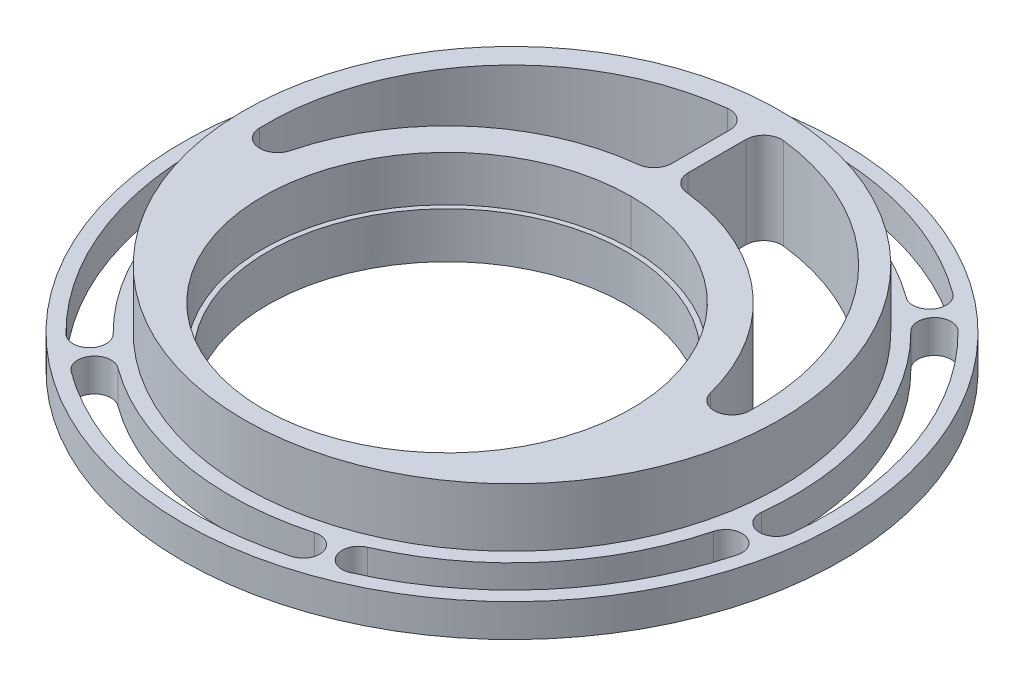
SolidWorks part; units mm, degrees
material "7075-T6, Plate (SS)"
ref_plane "X-Y Datum" through (0, 0, 0) normal (0, 0, 1) x (1, 0, 0)
ref_plane "X-Z Datum" through (0, 0, 0) normal (0, 1, 0) x (1, 0, 0)
ref_plane "Y-Z Datum" through (0, 0, 0) normal (1, 0, 0) x (0, 0, -1)
sketch "Sketch1" plane through (0, 0, 0) normal (0, 1, 0) x (1, 0, 0)
  line L0 (0, 0) -> (0, -12.7) construction
  line L1 (0, -43.0151) -> (0, 43.0151) construction
  line L2 (0, 61.9125) -> (0, 52.3875)
  circle A0 centre (0, -12.7) radius 35.052
  circle A1 centre (0, 0) radius 52.3875 construction
  circle A2 centre (0, 0) radius 57.15 construction
  circle A3 centre (0, 0) radius 61.9125
  point P12 (0, 57.15)
  dimension "D2" = 70.104
  dimension "D3" = 104.775
  dimension "D4" = 123.825
  dimension "D5" = 114.3
  dimension "D1" = 12.7
extrude "Boss-Extrude1" add sketch "Sketch1" along normal blind 4.5212 contours A3 A0 region at (-42.5405, 0, 42.5405)
sketch "Sketch3" plane through (0, 4.5212, 0) normal (0, 1, 0) x (1, 0, 0)
  circle A0 centre (0, 0) radius 52.3875 construction
  circle A1 centre (0, 0) radius 52.3875
extrude "Boss-Extrude2" add sketch "Sketch3" along normal blind 11.43
sketch "Sketch4" plane through (0, 0, 0) normal (0, -1, 0) x (1, 0, 0)
  circle A0 centre (0, 12.7) radius 35.052 construction
  circle A1 centre (0, 12.7) radius 35.052
extrude "Cut-Extrude1" cut sketch "Sketch4" against normal through all
sketch "Sketch9" plane through (0, 15.9512, 0) normal (0, 1, 0) x (1, 0, 0)
  circle A0 centre (0, -12.7) radius 35.052 construction
  circle A1 centre (0, -12.7) radius 35.052 construction
  circle A2 centre (0, -12.7) radius 36
  dimension "D1" = 72
extrude "Cut-Extrude3" cut sketch "Sketch9" against normal blind 8.89
ref_point "Point1"
ref_plane "Plane1" through (0, 0, 0) normal (1, 0, 0) x (0, 0, -1)
split line "Split Line1"
ref_plane "Plane2" through (0, 7.9756, 0) normal (0, 1, 0) x (1, 0, 0)
sketch "Sketch14" plane through (0, 7.9756, 0) normal (0, 1, 0) x (1, 0, 0)
  circle A0 centre (-33.2491, 22.3603) radius 8.255
ref_point "Point4"
ref_point "Point6"
sketch "Sketch10" plane through (0, 15.9512, 0) normal (0, 1, 0) x (1, 0, 0)
  circle A0 centre (0, 0) radius 52.3875 construction
  circle A1 centre (0, 0) radius 52.3875 construction
  arc A7 (0, -52.764) -> (0, 27.364) centre (0, -12.7) ccw
  arc A8 (0, 27.364) -> (0, -52.764) centre (0, -12.7) ccw
  arc A9 (0, -52.764) -> (0, 27.364) centre (0, -12.7) ccw construction
  arc A10 (0, 27.364) -> (0, -52.764) centre (0, -12.7) ccw construction
  circle A29 centre (0, 0) radius 48.3235 construction
  arc A30 (-30.6977, 13.0444) -> (30.6977, 13.0444) centre (0, -12.7) cw
  arc A31 (-43.3761, 21.2996) -> (43.3761, 21.2996) centre (0, 0) cw
  arc A34 (-30.6977, 13.0444) -> (-43.3761, 21.2996) centre (-36.5363, 17.9409) cw
  arc A35 (43.3761, 21.2996) -> (30.6977, 13.0444) centre (36.5363, 17.9409) cw
  dimension "D3" = 7.62
  dimension "D1" = 4.064
  dimension "D2" = 4.064
extrude "Cut-Extrude5" [suppressed] cut sketch "Sketch10" against normal through all contours A35 A31 A34 A30
sketch "Sketch15" [suppressed] plane through (0, 7.9756, 0) normal (0, 1, 0) x (1, 0, 0)
  line L1 (-2.1171, 31.2835) -> (-2.1171, 43.3958)
  line L4 (2.032, 31.291) -> (2.032, 43.4389)
  line L6 (-2.1764, 48.3235) -> (-2.1667, 48.2749) construction
  line L8 (2.1667, 48.2749) -> (2.1764, 48.3235) construction
  arc A0 (30.6977, 13.0444) -> (-30.6977, 13.0444) centre (0, -12.7) ccw construction
  arc A1 (30.6977, 13.0444) -> (-30.6977, 13.0444) centre (0, -12.7) ccw construction
  arc A2 (43.3761, 21.2996) -> (-43.3761, 21.2996) centre (0, 0) ccw construction
  arc A3 (-2.1171, 43.3958) -> (-6.9062, 47.8275) centre (-6.5621, 43.3958) ccw
  arc A4 (43.3761, 21.2996) -> (-43.3761, 21.2996) centre (0, 0) ccw construction
  arc A5 (6.5037, 47.8838) -> (2.032, 43.4389) centre (6.477, 43.4389) ccw
  arc A7 (-2.1171, 31.2835) -> (-5.362, 27.0036) centre (-6.5621, 31.2835) cw
  arc A9 (2.032, 31.291) -> (5.2509, 27.0184) centre (6.477, 31.291) ccw
  arc A10 (-6.9062, 47.8275) -> (6.5037, 47.8838) centre (0, 0) cw
  arc A11 (-5.362, 27.0036) -> (5.2509, 27.0184) centre (0, -12.7) cw
  point P9 (0, 37.4715)
  dimension "D1" = 4.445
  dimension "D2" = 2.1171
  dimension "D3" = 4.445
  dimension "D4" = 2.032
  dimension "D5" = 43.4389
  dimension "D6" = 31.2835
  dimension "D7" = 2.1171
  dimension "D8" = 12.148
  dimension "D9" = 12.1123
extrude "Boss-Extrude3" [suppressed] add sketch "Sketch15" along normal up to surface and the other way up to surface contours A9 L4 A5 A10 A3 L1 A7 A11
sketch "Sketch20" plane through (0, 4.5212, 0) normal (0, 1, 0) x (1, 0, 0)
  circle A0 centre (0, 0) radius 52.3875
  circle A2 centre (0, 0) radius 66.6087
sketch "Sketch25" [suppressed] plane through (0, 15.9512, 0) normal (0, 1, 0) x (1, 0, 0)
  line L6 (-4.6571, 31.2835) -> (-4.6571, 43.3958)
  line L7 (-4.6571, 31.2835) -> (-4.6571, 43.3958)
  line L12 (4.572, 43.4389) -> (4.572, 31.291)
  line L13 (4.572, 43.4389) -> (4.572, 31.291)
  circle A1 centre (-51.685, -7.6867) radius 0.134
  circle A2 centre (49.3335, -18.9489) radius 0.46
  arc A3 (48.8818, -18.8622) -> (48.9404, -18.71) centre (-0.2183, 0.1504) ccw
  arc A4 (48.8818, -18.8622) -> (48.9404, -18.71) centre (-0.2183, 0.1504) ccw
  arc A45 (-4.6571, 43.3958) -> (-6.6423, 45.2991) centre (-6.5621, 43.3958) ccw
  arc A46 (-5.9167, 29.4912) -> (-4.6571, 31.2835) centre (-6.5621, 31.2835) ccw
  arc A47 (-5.9167, 29.4912) -> (-32.6439, 14.6766) centre (0, -12.7) ccw
  arc A48 (-41.0962, 20.18) -> (-32.6439, 14.6766) centre (-36.5363, 17.9409) ccw
  arc A49 (-6.6423, 45.2991) -> (-41.0962, 20.18) centre (0, 0) ccw
  arc A50 (-4.6571, 43.3958) -> (-6.6423, 45.2991) centre (-6.5621, 43.3958) ccw
  arc A51 (-5.9167, 29.4912) -> (-4.6571, 31.2835) centre (-6.5621, 31.2835) ccw
  arc A52 (-5.9167, 29.4912) -> (-32.6439, 14.6766) centre (0, -12.7) ccw
  arc A53 (-41.0962, 20.18) -> (-32.6439, 14.6766) centre (-36.5363, 17.9409) ccw
  arc A54 (-6.6423, 45.2991) -> (-41.0962, 20.18) centre (0, 0) ccw
  circle A68 centre (-0.2183, 0.1504) radius 52.1224
  circle A69 centre (0, -12.7) radius 32.512
  circle A70 centre (0, -12.7) radius 32.512
  arc A72 (32.6439, 14.6766) -> (41.0962, 20.18) centre (36.5363, 17.9409) ccw
  arc A73 (4.572, 31.291) -> (5.8124, 29.5056) centre (6.477, 31.291) ccw
  arc A74 (32.6439, 14.6766) -> (5.8124, 29.5056) centre (0, -12.7) ccw
  arc A75 (41.0962, 20.18) -> (6.3564, 45.3401) centre (0, 0) ccw
  arc A76 (6.3564, 45.3401) -> (4.572, 43.4389) centre (6.477, 43.4389) ccw
  arc A77 (32.6439, 14.6766) -> (41.0962, 20.18) centre (36.5363, 17.9409) ccw
  arc A78 (4.572, 31.291) -> (5.8124, 29.5056) centre (6.477, 31.291) ccw
  arc A79 (32.6439, 14.6766) -> (5.8124, 29.5056) centre (0, -12.7) ccw
  arc A80 (41.0962, 20.18) -> (6.3564, 45.3401) centre (0, 0) ccw
  arc A81 (6.3564, 45.3401) -> (4.572, 43.4389) centre (6.477, 43.4389) ccw
  arc M3 (30.6977, 13.0444) -> (5.2509, 27.0184) centre (0, -12.7) ccw
  arc M4 (5.2509, 27.0184) -> (2.032, 31.291) centre (6.477, 31.291) cw
  line M5 (2.032, 31.291) -> (2.032, 43.4389)
  arc M6 (2.032, 43.4389) -> (6.5037, 47.8838) centre (6.477, 43.4389) cw
  arc M7 (6.5037, 47.8838) -> (43.3761, 21.2996) centre (0, 0) cw
  arc M8 (43.3761, 21.2996) -> (30.6977, 13.0444) centre (36.5363, 17.9409) cw
  arc M9 (-5.362, 27.0036) -> (-30.6977, 13.0444) centre (0, -12.7) ccw
  arc M10 (-30.6977, 13.0444) -> (-43.3761, 21.2996) centre (-36.5363, 17.9409) cw
  arc M11 (-43.3761, 21.2996) -> (-6.9062, 47.8275) centre (0, 0) cw
  arc M12 (-6.9062, 47.8275) -> (-2.1171, 43.3958) centre (-6.5621, 43.3958) cw
  line M13 (-2.1171, 43.3958) -> (-2.1171, 31.2835)
  arc M14 (-2.1171, 31.2835) -> (-5.362, 27.0036) centre (-6.5621, 31.2835) cw
  arc M15 (0, 23.3) -> (0, -48.7) centre (0, -12.7) cw
  arc M16 (0, -48.7) -> (0, 23.3) centre (0, -12.7) cw
  dimension "D1" = 2.54
  dimension "D2" = 2.54
  dimension "D3" = 2.54
extrude "Boss-Extrude5" [suppressed] add sketch "Sketch25" along normal blind 1.27 contours A54 A50 L7 A51 A52 A53 M9 M14 M13 M12 M11 M10 | A70 M15 M16 | A68 A1 M16 M15 M14 M9 M10 M11 M12 M13 M8 M3 M4 M5 M6 M7 | A81 A80 A77 A79 A78 L13 M3 M8 M7 M6 M5 M4
ref_axis "Axis1" [suppressed] through (0, 0, 0) along (0, 0, -1)
sketch "Sketch26" plane through (0, 4.5212, 0) normal (0, 1, 0) x (1, 0, 0)
  line L0 (0, 0) -> (-57.7152, 9.6181)
  line L1 (0, 0) -> (-38.741, -43.8484)
  arc A0 (-58.0713, 6.3737) -> (-41.0626, -41.5543) centre (0, 0) ccw construction
  arc A1 (-61.3157, 6.7298) -> (-43.3568, -43.8759) centre (0, 0) ccw
  arc A2 (-54.8269, 6.0176) -> (-38.7685, -39.2327) centre (0, 0) ccw
  arc A3 (-54.8269, 6.0176) -> (-61.3157, 6.7298) centre (-58.0713, 6.3737) ccw
  arc A4 (-43.3568, -43.8759) -> (-38.7685, -39.2327) centre (-41.0626, -41.5543) ccw
  point P4 (-55.0559, -19.5382)
  dimension "D2" = 3.2639
  dimension "D4" = 6.5278
  dimension "D1" = 58.42
  dimension "D3" = 58
extrude "Cut-Extrude6" cut sketch "Sketch26" against normal up to surface (4.5212 mm away) contours A2 A4 A1 A3 up to face at (0, 0, 47.752)
pattern_circular "CirPattern2" count 6 over 360 about axis through (0, 4.5212, 0) along (0, 1, 0) of "Cut-Extrude6"
sketch "Sketch27" plane through (0, 15.9512, 0) normal (0, 1, 0) x (1, 0, 0)
  line L0 (0, 0) -> (0, 50000) construction
  line L3 (-1.5875, 44.1588) -> (-1.5875, 32.8602)
  line L5 (1.5875, 44.1588) -> (1.5875, 32.8602)
  arc A9 (-41.0432, -2.2608) -> (-47.9187, -1.5099) centre (-44.428, -1.3999) cw
  arc A18 (-5.4791, 47.6284) -> (-47.9187, -1.5099) centre (0, 0) ccw
  arc A19 (-4.693, 29.3892) -> (-41.0432, -2.2608) centre (0, -12.7) ccw
  arc A20 (-5.4791, 47.6284) -> (-1.5875, 44.1588) centre (-5.08, 44.1588) cw
  arc A21 (-1.5875, 32.8602) -> (-4.693, 29.3892) centre (-5.08, 32.8602) cw
  arc A22 (1.5875, 32.8602) -> (4.693, 29.3892) centre (5.08, 32.8602) ccw
  arc A23 (5.4791, 47.6284) -> (1.5875, 44.1588) centre (5.08, 44.1588) ccw
  arc A24 (4.693, 29.3892) -> (41.0432, -2.2608) centre (0, -12.7) cw
  arc A25 (5.4791, 47.6284) -> (47.9187, -1.5099) centre (0, 0) cw
  arc A26 (41.0432, -2.2608) -> (47.9187, -1.5099) centre (44.428, -1.3999) ccw
  point P18 (-1.5875, 47.9162)
  point P22 (1.5875, 47.9162)
  dimension "D3" = 3.4925
  dimension "D2" = 3.4925
extrude "Cut-Extrude7" cut sketch "Sketch27" against normal through all both and the other way through all
sketch "Sketch28" plane through (0, 0, 0) normal (0, -1, 0) x (1, 0, 0)
  line L1 (1.5875, -32.8602) -> (1.5875, -44.1588)
  line L2 (1.5875, -32.8602) -> (1.5875, -44.1588)
  line L3 (-1.5875, -44.1588) -> (-1.5875, -32.8602)
  line L4 (-1.5875, -44.1588) -> (-1.5875, -32.8602)
  circle A6 centre (0, 12.7) radius 35.052
  circle A7 centre (0, 12.7) radius 35.052
  arc A11 (-38.7685, 39.2327) -> (-54.8269, -6.0176) centre (0, 0) ccw
  arc A12 (-61.3157, -6.7298) -> (-54.8269, -6.0176) centre (-58.0713, -6.3737) ccw
  arc A13 (-43.3568, 43.8759) -> (-61.3157, -6.7298) centre (0, 0) ccw
  arc A14 (-38.7685, 39.2327) -> (-43.3568, 43.8759) centre (-41.0626, 41.5543) ccw
  arc A15 (-38.7685, 39.2327) -> (-54.8269, -6.0176) centre (0, 0) ccw
  arc A16 (-61.3157, -6.7298) -> (-54.8269, -6.0176) centre (-58.0713, -6.3737) ccw
  arc A17 (-43.3568, 43.8759) -> (-61.3157, -6.7298) centre (0, 0) ccw
  arc A18 (-38.7685, 39.2327) -> (-43.3568, 43.8759) centre (-41.0626, 41.5543) ccw
  arc A19 (14.5923, 53.1908) -> (-32.6248, 44.4727) centre (0, 0) ccw
  arc A20 (-36.486, 49.7361) -> (-32.6248, 44.4727) centre (-34.5554, 47.1044) ccw
  arc A21 (16.3193, 59.486) -> (-36.486, 49.7361) centre (0, 0) ccw
  arc A22 (14.5923, 53.1908) -> (16.3193, 59.486) centre (15.4558, 56.3384) ccw
  arc A23 (14.5923, 53.1908) -> (-32.6248, 44.4727) centre (0, 0) ccw
  arc A24 (-36.486, 49.7361) -> (-32.6248, 44.4727) centre (-34.5554, 47.1044) ccw
  arc A25 (16.3193, 59.486) -> (-36.486, 49.7361) centre (0, 0) ccw
  arc A26 (14.5923, 53.1908) -> (16.3193, 59.486) centre (15.4558, 56.3384) ccw
  arc A27 (-53.3607, -13.9581) -> (-22.2021, -50.4902) centre (0, 0) ccw
  arc A28 (-24.8297, -56.4658) -> (-22.2021, -50.4902) centre (-23.5159, -53.478) ccw
  arc A29 (-59.676, -15.6101) -> (-24.8297, -56.4658) centre (0, 0) ccw
  arc A30 (-53.3607, -13.9581) -> (-59.676, -15.6101) centre (-56.5184, -14.7841) ccw
  arc A31 (-53.3607, -13.9581) -> (-22.2021, -50.4902) centre (0, 0) ccw
  arc A32 (-24.8297, -56.4658) -> (-22.2021, -50.4902) centre (-23.5159, -53.478) ccw
  arc A33 (-59.676, -15.6101) -> (-24.8297, -56.4658) centre (0, 0) ccw
  arc A34 (-53.3607, -13.9581) -> (-59.676, -15.6101) centre (-56.5184, -14.7841) ccw
  arc A35 (-14.5923, -53.1908) -> (32.6248, -44.4727) centre (0, 0) ccw
  arc A36 (36.486, -49.7361) -> (32.6248, -44.4727) centre (34.5554, -47.1044) ccw
  arc A37 (-16.3193, -59.486) -> (36.486, -49.7361) centre (0, 0) ccw
  arc A38 (-14.5923, -53.1908) -> (-16.3193, -59.486) centre (-15.4558, -56.3384) ccw
  arc A39 (-14.5923, -53.1908) -> (32.6248, -44.4727) centre (0, 0) ccw
  arc A40 (36.486, -49.7361) -> (32.6248, -44.4727) centre (34.5554, -47.1044) ccw
  arc A41 (-16.3193, -59.486) -> (36.486, -49.7361) centre (0, 0) ccw
  arc A42 (-14.5923, -53.1908) -> (-16.3193, -59.486) centre (-15.4558, -56.3384) ccw
  arc A43 (38.7685, -39.2327) -> (54.8269, 6.0176) centre (0, 0) ccw
  arc A44 (61.3157, 6.7298) -> (54.8269, 6.0176) centre (58.0713, 6.3737) ccw
  arc A45 (43.3568, -43.8759) -> (61.3157, 6.7298) centre (0, 0) ccw
  arc A46 (38.7685, -39.2327) -> (43.3568, -43.8759) centre (41.0626, -41.5543) ccw
  arc A47 (38.7685, -39.2327) -> (54.8269, 6.0176) centre (0, 0) ccw
  arc A48 (61.3157, 6.7298) -> (54.8269, 6.0176) centre (58.0713, 6.3737) ccw
  arc A49 (43.3568, -43.8759) -> (61.3157, 6.7298) centre (0, 0) ccw
  arc A50 (38.7685, -39.2327) -> (43.3568, -43.8759) centre (41.0626, -41.5543) ccw
  arc A51 (53.3607, 13.9581) -> (22.2021, 50.4902) centre (0, 0) ccw
  arc A52 (24.8297, 56.4658) -> (22.2021, 50.4902) centre (23.5159, 53.478) ccw
  arc A53 (59.676, 15.6101) -> (24.8297, 56.4658) centre (0, 0) ccw
  arc A54 (53.3607, 13.9581) -> (59.676, 15.6101) centre (56.5184, 14.7841) ccw
  arc A55 (53.3607, 13.9581) -> (22.2021, 50.4902) centre (0, 0) ccw
  arc A56 (24.8297, 56.4658) -> (22.2021, 50.4902) centre (23.5159, 53.478) ccw
  arc A57 (59.676, 15.6101) -> (24.8297, 56.4658) centre (0, 0) ccw
  arc A58 (53.3607, 13.9581) -> (59.676, 15.6101) centre (56.5184, 14.7841) ccw
  arc A60 (4.693, -29.3892) -> (1.5875, -32.8602) centre (5.08, -32.8602) ccw
  arc A61 (4.693, -29.3892) -> (41.0432, 2.2608) centre (0, 12.7) ccw
  arc A62 (47.9187, 1.5099) -> (41.0432, 2.2608) centre (44.428, 1.3999) ccw
  arc A63 (5.4791, -47.6284) -> (47.9187, 1.5099) centre (0, 0) ccw
  arc A64 (1.5875, -44.1588) -> (5.4791, -47.6284) centre (5.08, -44.1588) ccw
  arc A65 (4.693, -29.3892) -> (1.5875, -32.8602) centre (5.08, -32.8602) ccw
  arc A66 (4.693, -29.3892) -> (41.0432, 2.2608) centre (0, 12.7) ccw
  arc A67 (47.9187, 1.5099) -> (41.0432, 2.2608) centre (44.428, 1.3999) ccw
  arc A68 (5.4791, -47.6284) -> (47.9187, 1.5099) centre (0, 0) ccw
  arc A69 (1.5875, -44.1588) -> (5.4791, -47.6284) centre (5.08, -44.1588) ccw
  arc A70 (-5.4791, -47.6284) -> (-1.5875, -44.1588) centre (-5.08, -44.1588) ccw
  arc A71 (-47.9187, 1.5099) -> (-5.4791, -47.6284) centre (0, 0) ccw
  arc A72 (-41.0432, 2.2608) -> (-47.9187, 1.5099) centre (-44.428, 1.3999) ccw
  arc A73 (-41.0432, 2.2608) -> (-4.693, -29.3892) centre (0, 12.7) ccw
  arc A74 (-1.5875, -32.8602) -> (-4.693, -29.3892) centre (-5.08, -32.8602) ccw
  arc A75 (-5.4791, -47.6284) -> (-1.5875, -44.1588) centre (-5.08, -44.1588) ccw
  arc A76 (-47.9187, 1.5099) -> (-5.4791, -47.6284) centre (0, 0) ccw
  arc A77 (-41.0432, 2.2608) -> (-47.9187, 1.5099) centre (-44.428, 1.3999) ccw
  arc A78 (-41.0432, 2.2608) -> (-4.693, -29.3892) centre (0, 12.7) ccw
  arc A79 (-1.5875, -32.8602) -> (-4.693, -29.3892) centre (-5.08, -32.8602) ccw
  arc M39 (53.3607, 13.9581) -> (22.2021, 50.4902) centre (0, 0) ccw
  arc M40 (22.2021, 50.4902) -> (24.8297, 56.4658) centre (23.5159, 53.478) cw
  arc M41 (24.8297, 56.4658) -> (59.676, 15.6101) centre (0, 0) cw
  arc M42 (59.676, 15.6101) -> (53.3607, 13.9581) centre (56.5184, 14.7841) cw
  arc M43 (38.7685, -39.2327) -> (54.8269, 6.0176) centre (0, 0) ccw
  arc M44 (54.8269, 6.0176) -> (61.3157, 6.7298) centre (58.0713, 6.3737) cw
  arc M45 (61.3157, 6.7298) -> (43.3568, -43.8759) centre (0, 0) cw
  arc M46 (43.3568, -43.8759) -> (38.7685, -39.2327) centre (41.0626, -41.5543) cw
  arc M47 (-14.5923, -53.1908) -> (32.6248, -44.4727) centre (0, 0) ccw
  arc M48 (32.6248, -44.4727) -> (36.486, -49.7361) centre (34.5554, -47.1044) cw
  arc M49 (36.486, -49.7361) -> (-16.3193, -59.486) centre (0, 0) cw
  arc M50 (-16.3193, -59.486) -> (-14.5923, -53.1908) centre (-15.4558, -56.3384) cw
  arc M51 (-53.3607, -13.9581) -> (-22.2021, -50.4902) centre (0, 0) ccw
  arc M52 (-22.2021, -50.4902) -> (-24.8297, -56.4658) centre (-23.5159, -53.478) cw
  arc M53 (-24.8297, -56.4658) -> (-59.676, -15.6101) centre (0, 0) cw
  arc M54 (-59.676, -15.6101) -> (-53.3607, -13.9581) centre (-56.5184, -14.7841) cw
  arc M55 (14.5923, 53.1908) -> (-32.6248, 44.4727) centre (0, 0) ccw
  arc M56 (-32.6248, 44.4727) -> (-36.486, 49.7361) centre (-34.5554, 47.1044) cw
  arc M57 (-36.486, 49.7361) -> (16.3193, 59.486) centre (0, 0) cw
  arc M58 (16.3193, 59.486) -> (14.5923, 53.1908) centre (15.4558, 56.3384) cw
  arc M59 (-38.7685, 39.2327) -> (-54.8269, -6.0176) centre (0, 0) ccw
  arc M60 (-54.8269, -6.0176) -> (-61.3157, -6.7298) centre (-58.0713, -6.3737) cw
  arc M61 (-61.3157, -6.7298) -> (-43.3568, 43.8759) centre (0, 0) cw
  arc M62 (-43.3568, 43.8759) -> (-38.7685, 39.2327) centre (-41.0626, 41.5543) cw
  circle M63 centre (0, 12.7) radius 35.052
  circle M64 centre (0, 0) radius 61.9125
  line M65 (1.5875, -44.1588) -> (1.5875, -32.8602)
  arc M66 (1.5875, -32.8602) -> (4.693, -29.3892) centre (5.08, -32.8602) cw
  arc M67 (4.693, -29.3892) -> (41.0432, 2.2608) centre (0, 12.7) ccw
  arc M68 (41.0432, 2.2608) -> (47.9187, 1.5099) centre (44.428, 1.3999) cw
  arc M69 (47.9187, 1.5099) -> (5.4791, -47.6284) centre (0, 0) cw
  arc M70 (5.4791, -47.6284) -> (1.5875, -44.1588) centre (5.08, -44.1588) cw
  line M71 (-1.5875, -32.8602) -> (-1.5875, -44.1588)
  arc M72 (-1.5875, -44.1588) -> (-5.4791, -47.6284) centre (-5.08, -44.1588) cw
  arc M73 (-5.4791, -47.6284) -> (-47.9187, 1.5099) centre (0, 0) cw
  arc M74 (-47.9187, 1.5099) -> (-41.0432, 2.2608) centre (-44.428, 1.3999) cw
  arc M75 (-41.0432, 2.2608) -> (-4.693, -29.3892) centre (0, 12.7) ccw
  arc M76 (-4.693, -29.3892) -> (-1.5875, -32.8602) centre (-5.08, -32.8602) cw
  dimension "D1" = 0
  dimension "D2" = 0
  dimension "D3" = 0
  dimension "D4" = 0
  dimension "D5" = 0
  dimension "D6" = 0
  dimension "D7" = 0
  dimension "D8" = 0
  dimension "D9" = 0
extrude "Boss-Extrude6" add sketch "Sketch28" along normal blind 1.905 contours M64 M76 M71 M72 M73 M74 M75 M70 M65 M66 M67 M68 M69 M63 M62 M59 M60 M61 M58 M55 M56 M57 M54 M51 M52 M53 M50 M47 M48 M49 M46 M43 M44 M45 M42 M39 M40 M41 region at (-61.7374, 0, 0)
sketch "Sketch29" plane through (0, 4.5212, 0) normal (0, 1, 0) x (1, 0, 0)
  circle A0 centre (0, 0) radius 61.9125
  circle A1 centre (0, 0) radius 64.4525
  dimension "D1" = 123.825
  dimension "D2" = 2.54
extrude "Boss-Extrude7" add sketch "Sketch29" against normal through all
equation "\"NumSlots\"= 3"
equation "\"SlotAngSpacing\"= 4deg"
equation "\"SlotAngDim\"= 360deg / \"NumSlots\""
equation "\"SlotDim\"= \"SlotAngDim\" - \"SlotAngSpacing\""
equation "\"CutoutEndRad\"= .3in"
equation "\"Slot_Length\"= 4 in"
